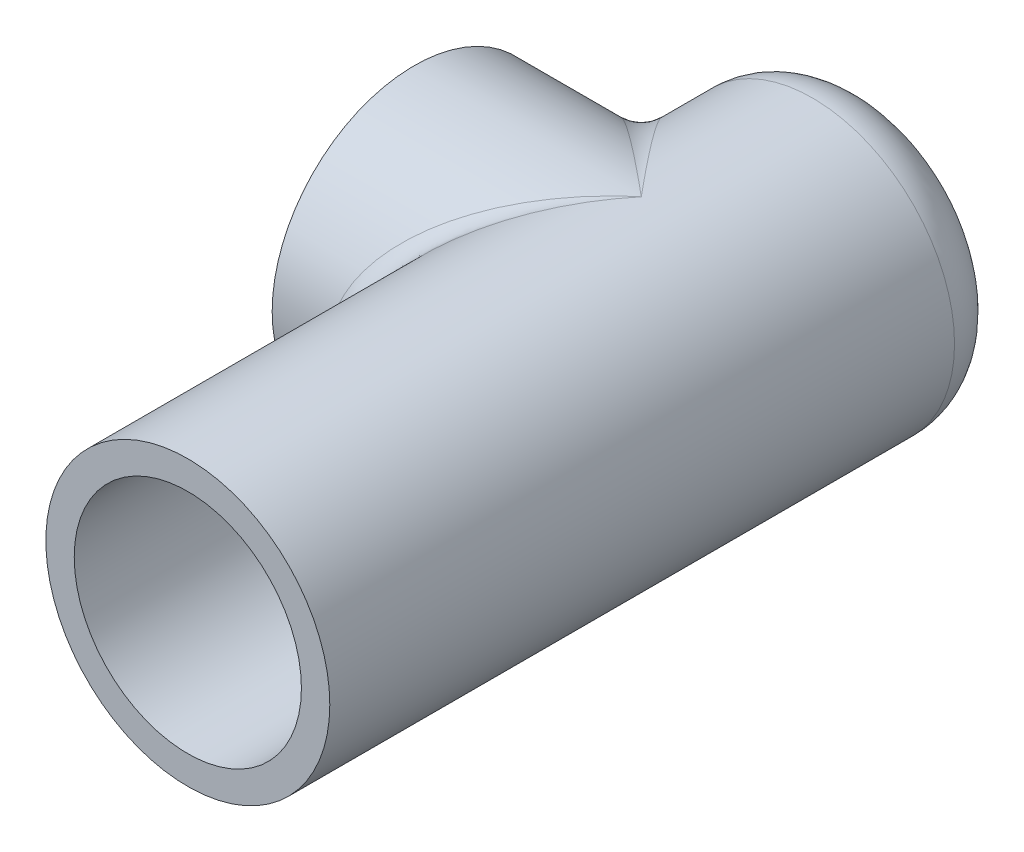
SolidWorks part; units mm, degrees
ref_plane "Front Plane" through (0, 0, 0) normal (0, 0, 1) x (1, 0, 0)
ref_plane "Top Plane" through (0, 0, 0) normal (0, 1, 0) x (1, 0, 0)
ref_plane "Right Plane" through (0, 0, 0) normal (1, 0, 0) x (0, 0, -1)
sketch "Sketch1" plane through (0, 0, 0) normal (0, 1, 0) x (1, 0, 0)
  line L0 (0, 0) -> (0, -120) construction
  line L1 (0, 0) -> (0, -40) construction
  line L2 (0, -40) -> (-40, -40) construction
  dimension "D1" = 40
  dimension "D2" = 40
  dimension "D3" = 120
ref_plane "Plane1" through (-40, 0, 40) normal (-1, 0, 0) x (0, 0, 1)
sketch "Sketch2" plane through (-40, 0, 40) normal (-1, 0, 0) x (0, 0, 1)
  line L0 (-40, 0) -> (80, 0) construction
  circle A0 centre (0.15, 0) radius 25
  circle A1 centre (0.15, 0) radius 20
ref_plane "Plane2" through (0, 0, 120) normal (0, 0, 1) x (1, 0, 0)
sketch "Sketch3" plane through (0, 0, 120) normal (0, 0, 1) x (1, 0, 0)
  circle A0 centre (0, 0) radius 25
  circle A1 centre (0, 0) radius 20
extrude "Boss-Extrude2" add sketch "Sketch3" against normal up to vertex (120 mm away) up to point (0, 0, 0)
extrude "Boss-Extrude3" add sketch "Sketch2" against normal up to surface (15 mm away) up to face at (25, 0, 0)
fillet "Fillet1" radius 5 2 edges at (-25, 0, 15.15) (-25, 0, 65.15)
ref_plane "Plane3" through (0, 0, 0) normal (0, 0, 1) x (1, 0, 0)
sketch "Sketch4" plane through (0, 0, 0) normal (0, 0, 1) x (1, 0, 0)
  circle A0 centre (0, 0) radius 25
extrude "Boss-Extrude4" add sketch "Sketch4" along normal blind 10
fillet "Fillet2" radius 10 1 edges at (25, 0, 0)
